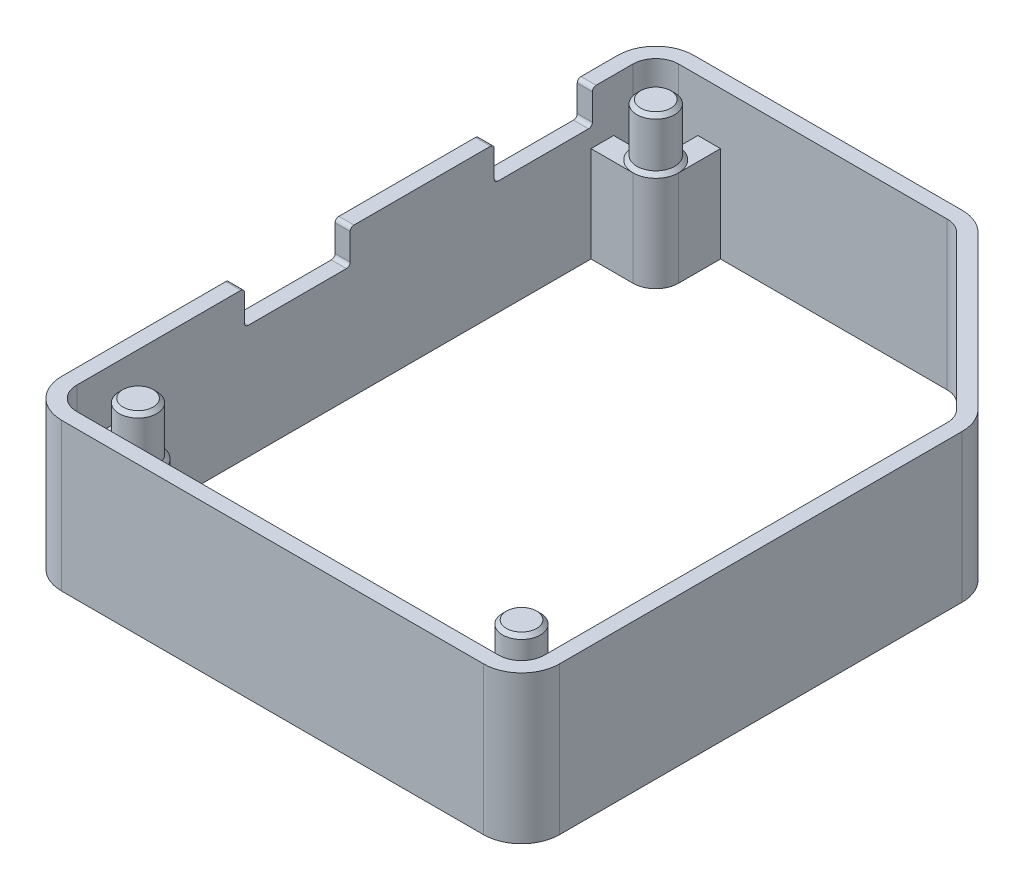
SolidWorks part; units mm, degrees
note: The reader was unsure of these and kept them because the rebuilt part matched: shared geometry of "Mounting_Base_Sketch<2>".
ref_plane "Front Plane" through (0, 0, 0) normal (0, 0, 1) x (1, 0, 0)
ref_plane "Top Plane" through (0, 0, 0) normal (0, 1, 0) x (1, 0, 0)
ref_plane "Right Plane" through (0, 0, 0) normal (1, 0, 0) x (0, 0, -1)
ref_plane "Base_Top_Plane" through (0, -11.07, 0) normal (0, -1, 0) x (-1, 0, 0)
sketch "PCB_Holes" plane through (0, -11.07, 0) normal (0, -1, 0) x (-1, 0, 0)
  circle A0 centre (-25.4001, -34.2901) radius 2.54 construction
  circle A1 centre (25.4001, -34.2901) radius 2.54 construction
  circle A2 centre (25.4001, 34.2901) radius 2.54 construction
  circle A3 centre (-25.4001, -34.2901) radius 2.54 construction
  circle A4 centre (25.4001, -34.2901) radius 2.54 construction
  circle A5 centre (25.4001, 34.2901) radius 2.54 construction
sketch "Base_Sketch" plane through (0, -11.07, 0) normal (0, -1, 0) x (-1, 0, 0)
  line L0 (-30.98, 16.51) -> (-30.98, -36.83)
  line L1 (-27.94, -39.87) -> (27.94, -39.87)
  line L2 (30.98, -36.83) -> (30.98, 36.83)
  line L3 (27.94, 39.87) -> (-7.62, 39.87)
  line L4 (-9.7696, 38.9796) -> (-30.0896, 18.6596)
  line L10 (-32.98, 16.51) -> (-32.98, -36.83)
  line L11 (-27.94, -41.87) -> (27.94, -41.87)
  line L12 (32.98, -36.83) -> (32.98, 36.83)
  line L13 (-11.1838, 40.3938) -> (-31.5038, 20.0738)
  line L14 (27.94, 41.87) -> (-7.62, 41.87)
  line L15 (-32.98, 16.51) -> (-32.98, -36.83)
  line L16 (-27.94, -41.87) -> (27.94, -41.87)
  line L17 (32.98, -36.83) -> (32.98, 36.83)
  line L18 (-11.1838, 40.3938) -> (-31.5038, 20.0738)
  line L19 (27.94, 41.87) -> (-7.62, 41.87)
  arc A0 (-30.0896, 18.6596) -> (-30.98, 16.51) centre (-27.94, 16.51) ccw
  arc A1 (-30.98, -36.83) -> (-27.94, -39.87) centre (-27.94, -36.83) ccw
  arc A2 (27.94, -39.87) -> (30.98, -36.83) centre (27.94, -36.83) ccw
  arc A3 (30.98, 36.83) -> (27.94, 39.87) centre (27.94, 36.83) ccw
  arc A4 (-7.62, 39.87) -> (-9.7696, 38.9796) centre (-7.62, 36.83) ccw
  arc A10 (-31.5038, 20.0738) -> (-32.98, 16.51) centre (-27.94, 16.51) ccw
  arc A11 (-32.98, -36.83) -> (-27.94, -41.87) centre (-27.94, -36.83) ccw
  arc A12 (27.94, -41.87) -> (32.98, -36.83) centre (27.94, -36.83) ccw
  arc A13 (32.98, 36.83) -> (27.94, 41.87) centre (27.94, 36.83) ccw
  arc A14 (-7.62, 41.87) -> (-11.1838, 40.3938) centre (-7.62, 36.83) ccw
  arc A15 (-31.5038, 20.0738) -> (-32.98, 16.51) centre (-27.94, 16.51) ccw
  arc A16 (-32.98, -36.83) -> (-27.94, -41.87) centre (-27.94, -36.83) ccw
  arc A17 (27.94, -41.87) -> (32.98, -36.83) centre (27.94, -36.83) ccw
  arc A18 (32.98, 36.83) -> (27.94, 41.87) centre (27.94, 36.83) ccw
  arc A19 (-7.62, 41.87) -> (-11.1838, 40.3938) centre (-7.62, 36.83) ccw
  dimension "D1" = 2.5
  dimension "D2" = 2
extrude "Walls" add sketch "Base_Sketch" along normal blind 1.6 and the other way blind 18
sketch "Port_Sketch" plane through (-32.98, 0, 0) normal (-1, 0, 0) x (0, 0, 1)
  line L0 (12.61, 8.6) -> (12.61, 5.6) construction
  line L1 (2.61, 8.6) -> (2.61, 5.6) construction
  line L2 (-20.47, 12.6) -> (-20.47, 1.6) construction
  line L3 (14.61, 2.43) -> (0.61, 2.43)
  line L4 (-29.47, 12.6) -> (-29.47, 1.6) construction
  line L5 (12.61, 8.6) -> (12.61, 5.6) construction
  line L6 (2.61, 8.6) -> (2.61, 5.6) construction
  line L7 (-20.47, 12.6) -> (-20.47, 1.6) construction
  line L9 (-29.47, 12.6) -> (-29.47, 1.6) construction
  line L10 (-31.47, 2.43) -> (-31.47, 6.93)
  line L12 (2.61, 5.6) -> (2.61, 2.43) construction
  line L13 (12.61, 5.6) -> (12.61, 2.43) construction
  line L14 (36.83, 6.93) -> (-36.83, 6.93) construction
  line L15 (-18.47, 2.43) -> (-18.47, 6.93)
  line L16 (0.61, 2.43) -> (0.61, 6.93)
  line L17 (14.61, 2.43) -> (14.61, 6.93)
  line L18 (-31.47, 6.93) -> (-18.47, 6.93)
  line L19 (0.61, 6.93) -> (14.61, 6.93)
  line L20 (-31.47, 2.43) -> (-18.47, 2.43)
  dimension "D1" = 2
  dimension "D2" = 2
  dimension "D3" = 2
  dimension "D4" = 2
  dimension "D5" = 4.5
  dimension "D6" = 4.5
extrude "Ports" cut sketch "Port_Sketch" against normal up to next
fillet "Port_Fillet" radius 0.5 8 edges at (-31.98, 6.93, 14.61) (-31.98, 6.93, 0.61) (-31.98, 6.93, -18.47) (-31.98, 6.93, -31.47) (-31.98, 2.43, -18.47) (-31.98, 2.43, -31.47) (-31.98, 2.43, 14.61) (-31.98, 2.43, 0.61)
sketch "Mounting_Base_Sketch" plane through (0, -11.07, 0) normal (0, -1, 0) x (-1, 0, 0)
  line L1 (-30.98, 16.51) -> (-30.98, -36.83) construction
  line L3 (-27.94, -39.87) -> (27.94, -39.87) construction
  line L5 (22.4001, -34.2901) -> (22.4001, -39.87)
  line L8 (22.4001, -39.87) -> (25.4001, -39.87)
  line L30 (-25.4001, -31.2901) -> (-30.98, -31.2901)
  line L31 (-22.4001, -34.2901) -> (-22.4001, -39.87)
  line L32 (-28.4001, -34.2901) -> (-30.98, -34.2901)
  line L33 (-30.98, -34.2901) -> (-30.98, -31.2901)
  line L34 (-25.4001, -37.2901) -> (-25.4001, -39.87)
  line L35 (-25.4001, -39.87) -> (-22.4001, -39.87)
  line L36 (25.4001, -39.87) -> (25.4001, -37.2901)
  line L42 (30.98, -36.83) -> (30.98, 36.83) construction
  line L43 (30.98, -34.2901) -> (28.4001, -34.2901)
  line L44 (25.4001, -31.2901) -> (30.98, -31.2901)
  line L45 (30.98, -34.2901) -> (30.98, -31.2901)
  line L52 (22.4001, 34.2901) -> (22.4001, 39.87)
  line L53 (22.4001, 39.87) -> (25.4001, 39.87)
  line L54 (25.4001, 39.87) -> (25.4001, 37.2901)
  line L55 (27.94, 39.87) -> (-7.62, 39.87) construction
  line L56 (25.4001, 31.2901) -> (30.98, 31.2901)
  line L57 (30.98, 31.2901) -> (30.98, 34.2901)
  line L58 (30.98, 34.2901) -> (28.4001, 34.2901)
  arc A0 (22.4001, -34.2901) -> (25.4001, -31.2901) centre (25.4001, -34.2901) cw
  arc A2 (25.4001, -37.2901) -> (28.4001, -34.2901) centre (25.4001, -34.2901) ccw
  circle A15 centre (-25.4001, -34.2901) radius 3 construction
  circle A16 centre (-25.4001, -34.2901) radius 2.5
  arc A17 (-25.4001, -31.2901) -> (-22.4001, -34.2901) centre (-25.4001, -34.2901) cw
  arc A18 (-28.4001, -34.2901) -> (-25.4001, -37.2901) centre (-25.4001, -34.2901) ccw
  circle A19 centre (25.4001, -34.2901) radius 3 construction
  circle A20 centre (25.4001, -34.2901) radius 2.5
  circle A22 centre (25.4001, 34.2901) radius 3 construction
  circle A23 centre (25.4001, 34.2901) radius 2.5
  arc A24 (22.4001, 34.2901) -> (25.4001, 31.2901) centre (25.4001, 34.2901) ccw
  arc A25 (25.4001, 37.2901) -> (28.4001, 34.2901) centre (25.4001, 34.2901) cw
  dimension "D1" = 6
  dimension "D2" = 5
  dimension "D3" = 6
  dimension "D4" = 5
  dimension "D5" = 6
  dimension "D6" = 5
extrude "Mounting_Base" add sketch "Mounting_Base_Sketch" along normal up to surface and the other way up to surface
extrude "Mounting_Pins" add sketch "Mounting_Base_Sketch<2>" against normal up to surface and the other way up to surface contours A16 | A20 | A23
sketch "Mounting_Base_Sketch<2>" plane through (0, -11.07, 0) normal (0, -1, 0) x (-1, 0, 0) same geometry as "Mounting_Base_Sketch"
surface "Wall_Knit"
chamfer "Mounting_Pin_Chamfer" distance 0.5 angle 45 6 edges at (-25.4001, 0, -36.7901) (25.4001, 0, 31.7901) (-25.4001, 0, 31.7901) (25.4001, 6.93, 31.7901) (-25.4001, 6.93, 31.7901) (-25.4001, 6.93, -36.7901)
